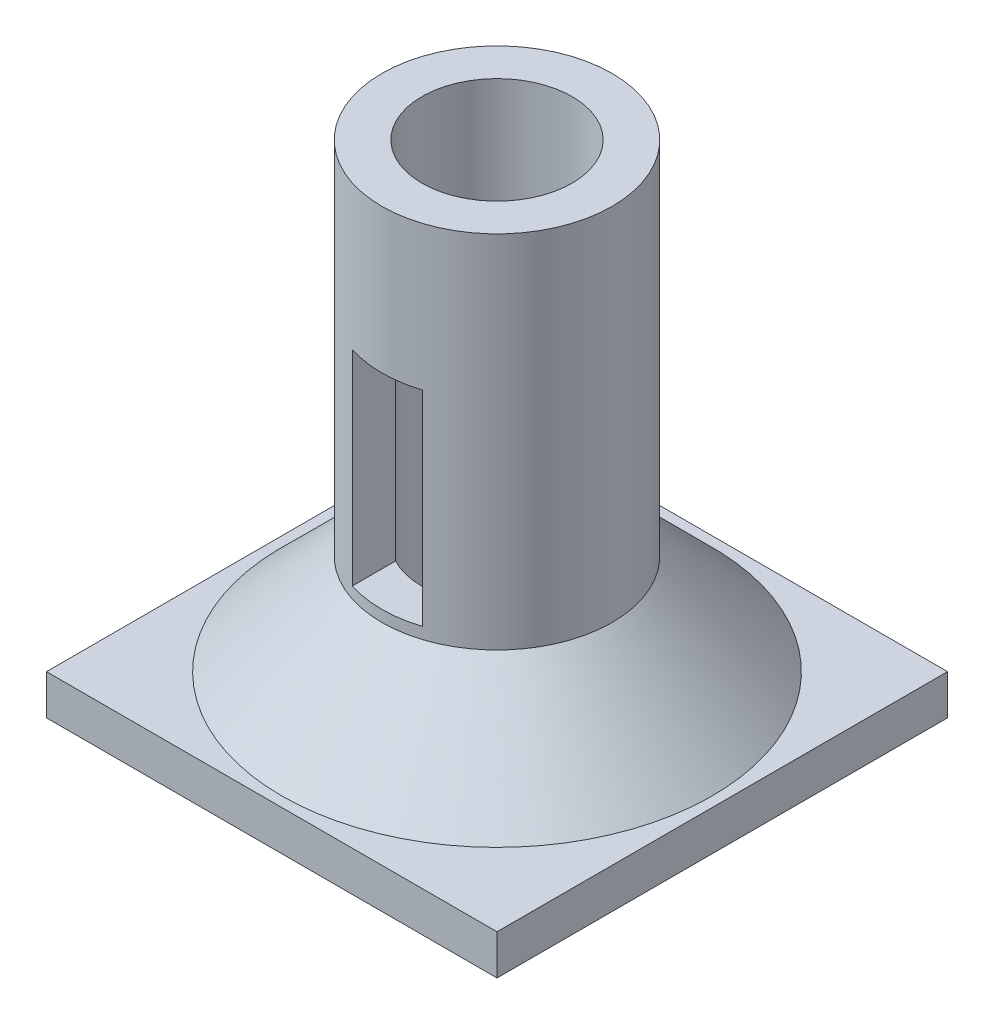
SolidWorks part; units mm, degrees
ref_plane "Front Plane" through (0, 0, 0) normal (0, 0, 1) x (1, 0, 0)
ref_plane "Top Plane" through (0, 0, 0) normal (0, 1, 0) x (1, 0, 0)
ref_plane "Right Plane" through (0, 0, 0) normal (1, 0, 0) x (0, 0, -1)
sketch "Sketch2" plane through (0, 0, 0) normal (0, 1, 0) x (1, 0, 0)
  line L1 (-22.5, 22.5) -> (22.5, 22.5)
  line L2 (-22.5, 22.5) -> (-22.5, -22.5)
  line L3 (-22.5, -22.5) -> (22.5, -22.5)
  line L4 (22.5, 22.5) -> (22.5, -22.5)
  circle A0 centre (0, 0) radius 7.5
  circle A1 centre (0, 0) radius 11.5
  dimension "D1" = 45
  dimension "D4" = 23
  dimension "D5" = 15
  dimension "D2" = 22.5
  dimension "D3" = 22.5
extrude "Boss-Extrude1" add sketch "Sketch2" against normal blind 4 contours L4 L1 L2 L3 A1 | A1 A0 | A0 region at (0, 0, -21.8636) region at (0, 0, 0) region at (-11.1747, 0, 0)
extrude "Boss-Extrude2" add sketch "Sketch2<3>" along normal blind 46 contours A1 A0 region at (-11.1747, 0, 0)
sketch "Sketch2<3>" plane through (0, 0, 0) normal (0, 1, 0) x (1, 0, 0) same geometry as "Sketch2"
chamfer "Chamfer1" distance 10 angle 45 1 edges at (0, 0, 11.5)
sketch "Sketch3" plane through (0, 0, 0) normal (0, 0, 1) x (1, 0, 0)
  line L0 (11.5, 10) -> (11.5, 46) construction
  line L1 (-3.5, 31.5881) -> (3.5, 31.5881)
  line L2 (-3.5, 31.5881) -> (-3.5, 11.1372)
  line L3 (-3.5, 11.1372) -> (3.5, 11.1372)
  line L4 (3.5, 31.5881) -> (3.5, 11.1372)
  point P4 (5.4391, 33.1835)
  dimension "D1" = 7
  dimension "D2" = 8
extrude "Cut-Extrude1" cut sketch "Sketch3" along normal blind 19
